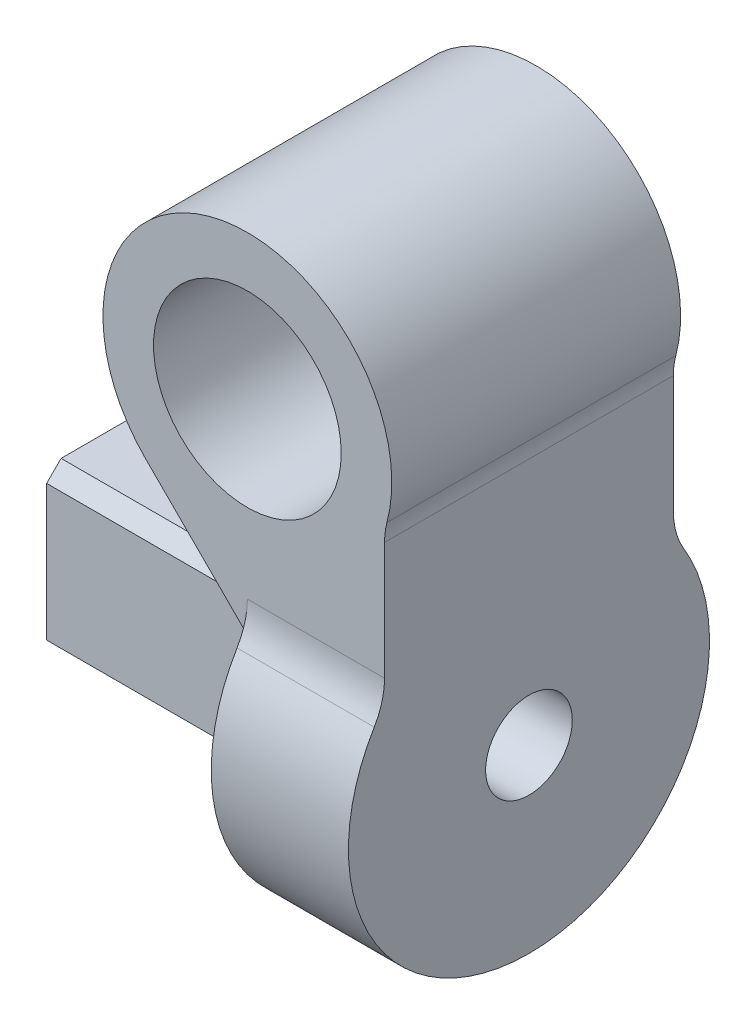
SolidWorks part; units mm, degrees
ref_plane "Front Plane" through (0, 0, 0) normal (0, 0, 1) x (1, 0, 0)
ref_plane "Top Plane" through (0, 0, 0) normal (0, 1, 0) x (1, 0, 0)
ref_plane "Right Plane" through (0, 0, 0) normal (1, 0, 0) x (0, 0, -1)
sketch "Sketch1" plane through (0, 0, 0) normal (1, 0, 0) x (0, 0, -1)
  circle A0 centre (0, 0) radius 62.5
  circle A1 centre (0, 0) radius 15
  dimension "D1" = 125
  dimension "D2" = 30
extrude "Boss-Extrude1" add sketch "Sketch1" along normal blind 47.5
sketch "Sketch2" plane through (0, 0, 0) normal (0, 0, 1) x (1, 0, 0)
  line L1 (0, 0) -> (0, 105) construction
  line L2 (-35.3553, 69.6447) -> (0, 34.2893)
  line L3 (0, 34.2893) -> (0, 55)
  arc A0 (0, 55) -> (-35.3553, 69.6447) centre (0, 105) ccw
  circle A1 centre (0, 105) radius 32.5
  arc A2 (-35.3553, 69.6447) -> (0, 55) centre (0, 105) ccw construction
  dimension "D1" = 100
  dimension "D2" = 65
  dimension "D3" = 105
  dimension "D4" = 45
extrude "Boss-Extrude2" add sketch "Sketch2" along normal mid plane 100
sketch "Sketch3" plane through (47.5, 0, 0) normal (1, 0, 0) x (0, 0, -1)
  line L0 (-50, 55) -> (-50, 62.5)
  line L1 (-50, 155) -> (-50, 55) construction
  line L2 (-50, 55) -> (-50, 37.5)
  line L3 (-29.6859, 55) -> (-50, 55)
  line L4 (-50, 55) -> (-50, 37.5)
  line L6 (50, 55) -> (29.6859, 55)
  line L7 (50, 37.5) -> (50, 55)
  line L9 (50, 37.5) -> (50, 55)
  line L10 (-50, 62.5) -> (50, 62.5)
  line L11 (50, 55) -> (50, 155) construction
  line L12 (50, 62.5) -> (50, 55)
  line L13 (29.6859, 55) -> (-29.6859, 55)
  circle A0 centre (0, 0) radius 62.5 construction
  arc A1 (-29.6859, 55) -> (-50, 37.5) centre (0, 0) ccw
  arc A2 (-29.6859, 55) -> (-50, 37.5) centre (0, 0) ccw
  arc A3 (50, 37.5) -> (29.6859, 55) centre (0, 0) ccw
  arc A4 (50, 37.5) -> (29.6859, 55) centre (0, 0) ccw
  dimension "D1" = 0
  dimension "D2" = 0
extrude "Boss-Extrude3" add sketch "Sketch3" against normal up to surface (47.5 mm away) up to face at (0, 49.5341, 43.5451)
sketch "Sketch4" plane through (0, 0, 50) normal (0, 0, 1) x (1, 0, 0)
  line L0 (47.5, 62.5) -> (47.5, 89.3875)
  line L1 (26.3391, 62.5) -> (47.5, 62.5) construction
  line L2 (26.3391, 62.5) -> (47.5, 62.5)
  arc A0 (26.3391, 62.5) -> (-35.3553, 69.6447) centre (0, 105) ccw construction
  arc A1 (26.3391, 62.5) -> (-35.3553, 69.6447) centre (0, 105) ccw
  line M2 (47.5, 62.5) -> (26.3391, 62.5)
  arc M3 (26.3391, 62.5) -> (-35.3553, 69.6447) centre (0, 105) ccw
extrude "Boss-Extrude4" add sketch "Sketch4" against normal up to surface (100 mm away) contours L0 M2 M3 region at (41.2754, 70.2611, 50) up to face at (16.0406, 65.4216, -50)
fillet "Fillet1" radius 25 3 edges at (23.75, 37.5, -50) (23.75, 37.5, 50) (47.5, 89.3875, 0)
sketch "Sketch5" plane through (0, 0, 0) normal (-1, 0, 0) x (0, 0, 1)
  line L1 (-28.5, -28.5) -> (28.5, -28.5)
  line L2 (-28.5, -28.5) -> (-28.5, 28.5)
  line L3 (-28.5, 28.5) -> (28.5, 28.5)
  line L4 (28.5, -28.5) -> (28.5, 28.5)
  line L5 (-28.5, -28.5) -> (28.5, 28.5) construction
  line L6 (-28.5, 28.5) -> (28.5, -28.5) construction
  point P0 (0, 0)
  dimension "D1" = 57
extrude "Boss-Extrude5" add sketch "Sketch5" along normal blind 91
chamfer "Chamfer1" distance 5 angle 45 4 edges at (-45.5, -28.5, 28.5) (-45.5, -28.5, -28.5) (-45.5, 28.5, 28.5) (-45.5, 28.5, -28.5)
